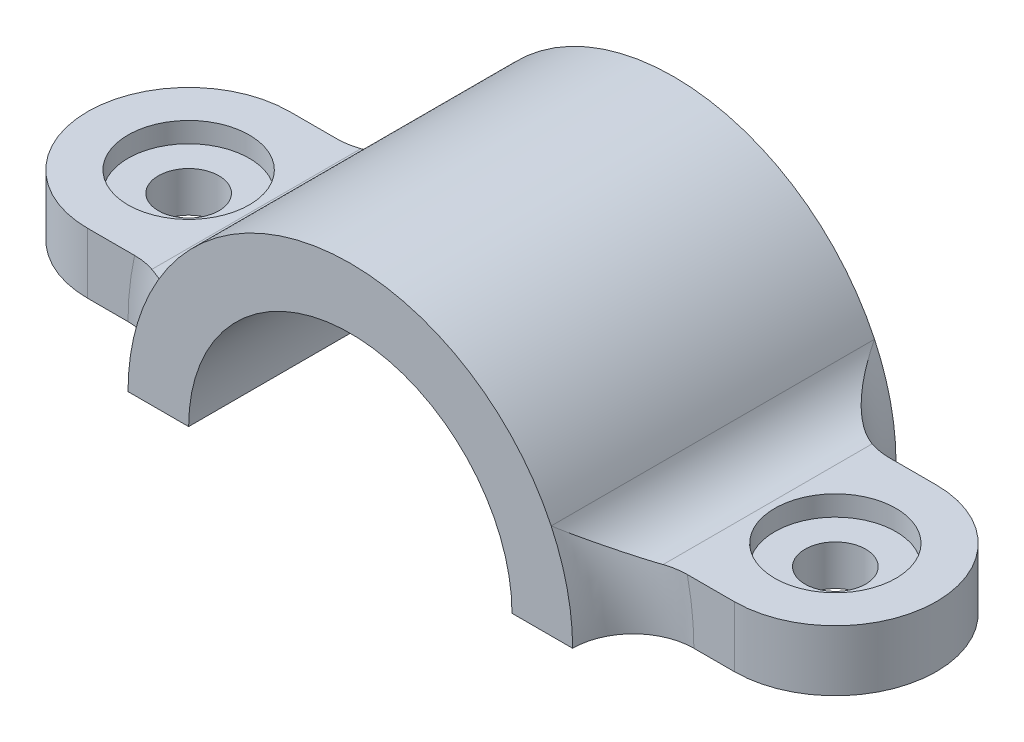
SolidWorks part; units mm, degrees
ref_plane "Front Plane" through (0, 0, 0) normal (0, 0, 1) x (1, 0, 0)
ref_plane "Top Plane" through (0, 0, 0) normal (0, 1, 0) x (1, 0, 0)
ref_plane "Right Plane" through (0, 0, 0) normal (1, 0, 0) x (0, 0, -1)
sketch "Sketch1" plane through (0, 0, 0) normal (0, 0, 1) x (1, 0, 0)
  line L0 (0, 0) -> (-41054.348, 0) construction
  line L1 (0, 0) -> (0, -41054.348) construction
  line L2 (-55, 0) -> (-40, 0)
  line L3 (40, 0) -> (55, 0)
  line L4 (55, 0) -> (105, 0)
  line L5 (105, 0) -> (105, 15)
  line L6 (105, 15) -> (52.915, 15)
  arc A0 (40, 0) -> (-40, 0) centre (0, 0) ccw
  arc A1 (55, 0) -> (-55, 0) centre (0, 0) ccw
  dimension "D1" = 40
  dimension "D2" = 55
  dimension "D3" = 50
  dimension "D4" = 15
extrude "Boss-Extrude1" add sketch "Sketch1" against normal blind 80 contours L3 A1 L2 A0 region at (-7.4028, 53.2581, 0)
extrude "Boss-Extrude2" add sketch "Sketch1<3>" against normal blind 50 from offset 15 contours A1 L4 L5 L6 region at (79.6514, 7.5512, 0) offset against normal yes
sketch "Sketch1<3>" plane through (0, 0, 0) normal (0, 0, 1) x (1, 0, 0) same geometry as "Sketch1"
fillet "Fillet1" 2 edges at (105, 7.5, -15) (105, 7.5, -65) type full round first side face at (79.6084, 7.518, -15) second side face at (79.6084, 7.518, -65) middle face at (105, 7.5, -40)
fillet "Fillet2" radius 15 2 edges at (54.4763, 7.5721, -65) (54.4763, 7.5721, -15)
fillet "Fillet3" radius 15 1 edges at (52.915, 15, -40)
hole_wizard "CBORE for M12 Hex Head Bolt1" positions "3DSketch1" profile "Sketch2" counterbore size "M12" standard "ANSI Metric" end condition through all
sketch3d "3DSketch1"
  line L0 (80, 0, -40) -> (80, 15, -40) construction
  point P0 (80, 15, -40)
sketch "Sketch2" plane through (80, 15, -40) normal (1, 0, 0) x (0, 0, 1)
  line L0 (0, 0) -> (0, 15)
  line L1 (0, 15) -> (7.5, 15)
  line L3 (7.5, 15) -> (7.5, 5)
  line L4 (7.5, 5) -> (15, 5)
  line L5 (15, 5) -> (15, 0)
  line L7 (15, 0) -> (0, 0)
  line L11 (0, -6.35) -> (0, 107.95) construction
  dimension "Thru Hole Dia." = 15
  dimension "Thru Hole Depth" = 15
  dimension "C'Bore Dia." = 30
  dimension "C'Bore Depth" = 5
mirror "Mirror1" about plane through (0, 0, 0) normal (1, 0, 0) of "Boss-Extrude2", "Fillet1", "Fillet2", "Fillet3", "CBORE for M12 Hex Head Bolt1"
